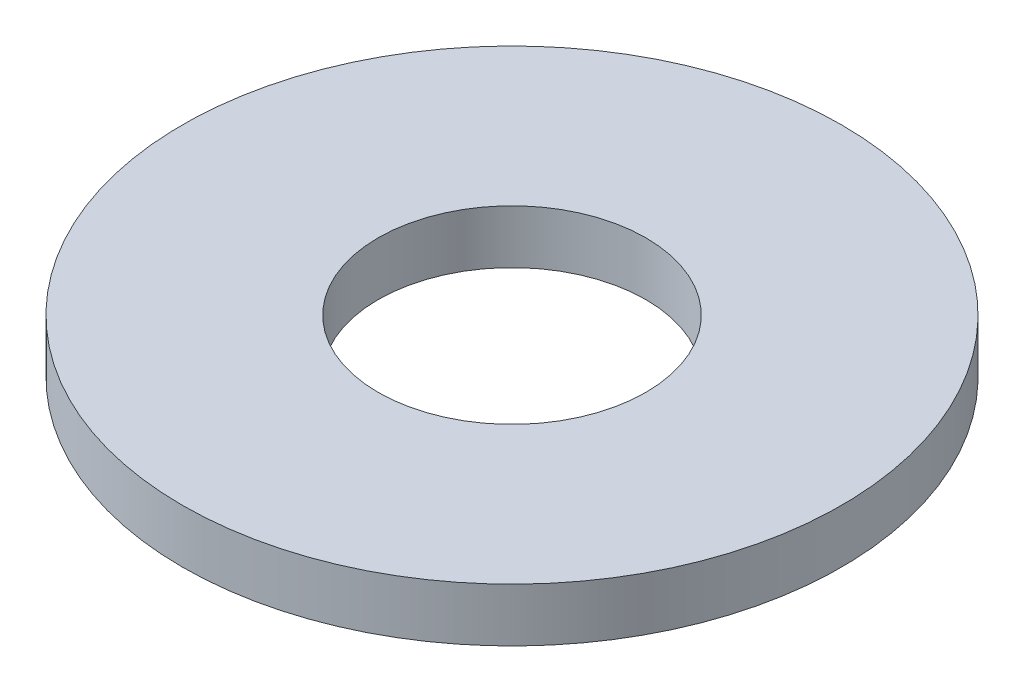
SolidWorks part; units mm, degrees
ref_plane "Front Plane" through (0, 0, 0) normal (0, 0, 1) x (1, 0, 0)
ref_plane "Top Plane" through (0, 0, 0) normal (0, 1, 0) x (1, 0, 0)
ref_plane "Right Plane" through (0, 0, 0) normal (1, 0, 0) x (0, 0, -1)
sketch "Sketch1" plane through (0, 0, 0) normal (0, 1, 0) x (1, 0, 0)
  circle A0 centre (0, 0) radius 80
  dimension "FLANGE_OD" = 160
extrude "Boss-Extrude1" add sketch "Sketch1" along normal blind 13
sketch "Sketch2" plane through (0, 0, 0) normal (0, 1, 0) x (1, 0, 0)
  circle A0 centre (0, 0) radius 32.5
  dimension "BORE_D" = 65
extrude "Cut-Extrude1" cut sketch "Sketch2" along normal through all
sketch "Sketch3" plane through (0, 13, 0) normal (0, 1, 0) x (1, 0, 0)
  circle A0 centre (0, 0) radius 21.2359 construction
  circle A1 centre (-21.2359, 0) radius 5.1157
  dimension "BOLT_D" = 10.2315
  dimension "BOLT_PCD" = 42.4719
extrude "Cut-Extrude2" cut sketch "Sketch3" against normal blind 11.8365 rebuild error yes
pattern_circular "CirPattern1" count 3 over 360 rebuild error yes
